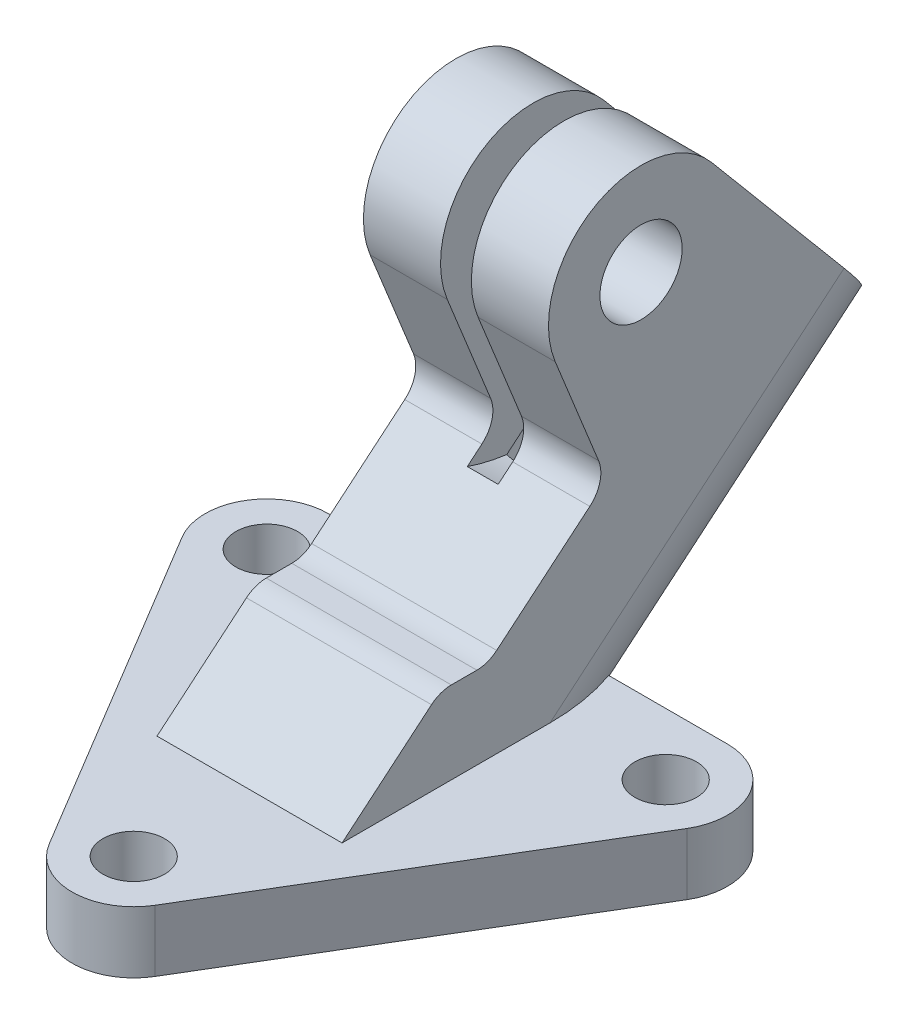
SolidWorks part; units mm, degrees
ref_plane "前视基准面" through (0, 0, 0) normal (0, 0, 1) x (1, 0, 0)
ref_plane "上视基准面" through (0, 0, 0) normal (0, 1, 0) x (1, 0, 0)
ref_plane "右视基准面" through (0, 0, 0) normal (1, 0, 0) x (0, 0, -1)
other "Configuration Table"
sketch "草图1" plane through (0, 0, 0) normal (0, 1, 0) x (1, 0, 0)
  line L0 (0, 38.3623) -> (0, -38.1044) construction
  line L7 (-19.4029, 25) -> (19.4029, 25)
  line L8 (24.5478, 15.913) -> (5.145, -16.4251)
  line L9 (-24.5478, 15.913) -> (-5.145, -16.4251)
  arc A0 (5.145, -16.4251) -> (-5.145, -16.4251) centre (0, -13.3381) cw
  arc A1 (-24.5478, 15.913) -> (-19.4029, 25) centre (-19.4029, 19) cw
  arc A2 (19.4029, 25) -> (24.5478, 15.913) centre (19.4029, 19) cw
  circle A3 centre (-19.4029, 19) radius 3
  circle A4 centre (19.4029, 19) radius 3
  circle A5 centre (0, -13.3381) radius 3
  point P8 (0, 25)
  point P10 (0, -25)
  point P14 (-30, 25)
  point P17 (30, 25)
  dimension "D4" = 6
  dimension "D5" = 6
  dimension "D1" = 50
  dimension "D2" = 60
  dimension "D3" = 25
extrude "凸台-拉伸1" add sketch "草图1" along normal blind 6
sketch "草图5" plane through (0, 0, 0) normal (1, 0, 0) x (0, 0, -1)
  line L0 (25, 0) -> (52.5362, 23.1056)
  line L1 (25, 0) -> (-9.2259, 0)
  line L2 (-16.4251, 0) -> (15.913, 0) construction
  line L3 (-9.2259, 0) -> (6.6222, 13.2981)
  line L4 (8.5505, 14) -> (11.0339, 14)
  line L5 (12.9622, 14.7019) -> (22.0209, 22.303)
  line L6 (22.8741, 25.7249) -> (18.6563, 36.1643)
  line L7 (52.5362, 23.1056) -> (33.8953, 45.3209)
  line L8 (-16.4251, 6) -> (15.913, 6) construction
  line L9 (46.7511, 30) -> (43.4845, 27.259) construction
  arc A0 (33.8953, 45.3209) -> (18.6563, 36.1643) centre (27.0009, 39.5358) ccw
  circle A1 centre (27.0009, 39.5358) radius 4
  arc A2 (22.0209, 22.303) -> (22.8741, 25.7249) centre (20.0925, 24.6011) ccw
  arc A3 (11.0339, 14) -> (12.9622, 14.7019) centre (11.0339, 17) ccw
  arc A4 (6.6222, 13.2981) -> (8.5505, 14) centre (8.5505, 11) cw
  point P15 (0, 0)
  point P22 (12.1258, 14)
  dimension "D5" = 18
  dimension "D9" = 8
  dimension "D11" = 3
  dimension "D1" = 40
  dimension "D2" = 22
  dimension "D3" = 8
  dimension "D4" = 108
  dimension "D6" = 9
  dimension "D7" = 20
  dimension "D8" = 30
  dimension "D10" = 3
extrude "凸台-拉伸2" add sketch "草图5" along normal mid plane 18
fillet "圆角1" 2 edges at (9, 11.5528, -38.7681) (-9, 11.5528, -38.7681) type full round first side face at (9, 39.5358, -31.0009) second side face at (-9, 39.5358, -31.0009) middle face at (0, 11.5528, -38.7681)
sketch "草图12" plane through (0, 0, 0) normal (1, 0, 0) x (0, 0, -1)
  line L0 (46.7511, 30) -> (-0.9191, -10)
  line L2 (-16.4251, 0) -> (15.913, 0) construction
  line L3 (18.149, 6) -> (46.7511, 30) construction
  line L4 (51.2506, 24.6377) -> (29.8014, 6.6396)
  line L5 (52.5362, 23.1056) -> (46.7511, 30) construction
  line L6 (29.8014, 6.6396) -> (26.9837, 6.8861)
  line L7 (26.9837, 6.8861) -> (6.8596, -10)
  line L10 (46.7511, 30) -> (51.2506, 24.6377)
  line L11 (-0.9191, -10) -> (6.8596, -10)
  dimension "D1" = 45
  dimension "D2" = 7
  dimension "D3" = 5
  dimension "D4" = 28
  dimension "D5" = 7
  dimension "D6" = 10
revolve "切除-旋转2" cut sketch "草图12" angle 360 about L0
sketch "草图14" plane through (0, 0, 0) normal (1, 0, 0) x (0, 0, -1)
  circle A0 centre (27.0009, 39.5358) radius 19.5
  dimension "D1" = 39
extrude "切除-拉伸1" cut sketch "草图14" against normal mid plane 3
